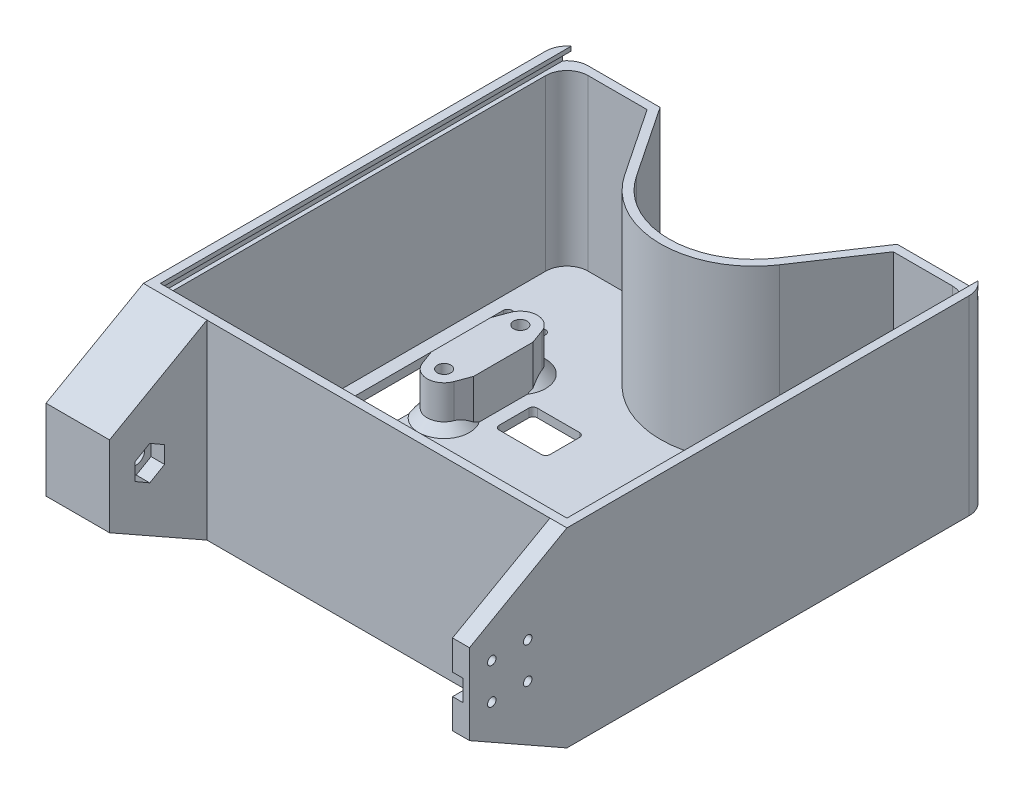
SolidWorks part; units mm, degrees
material "PVC hart"
ref_plane "Ebene vorne" through (0, 0, 0) normal (0, 0, 1) x (1, 0, 0)
ref_plane "Ebene oben" through (0, 0, 0) normal (0, 1, 0) x (1, 0, 0)
ref_plane "Ebene rechts" through (0, 0, 0) normal (1, 0, 0) x (0, 0, -1)
sketch "Grundplatte" plane through (0, 0, 0) normal (0, 1, 0) x (1, 0, 0)
  line L0 (0, 69.0751) -> (0, -94.5087) construction
  line L2 (-50, 50) -> (-50, -50)
  line L3 (-50, -50) -> (50, -50)
  line L4 (50, 50) -> (50, -50)
  line L5 (-50, 50) -> (50, -50) construction
  line L6 (-50, -50) -> (50, 50) construction
  line L7 (-50, 50) -> (-28, 50)
  line L8 (-28, 50) -> (-16.6199, 33)
  line L9 (28, 50) -> (16.6199, 33)
  line L10 (50, 50) -> (28, 50)
  arc A0 (-16.6199, 33) -> (16.6199, 33) centre (0, 44.1257) ccw
  point P0 (0, 0)
  dimension "D4" = 20
  dimension "D1" = 100
  dimension "D2" = 100
  dimension "D3" = 22
  dimension "D5" = 17
extrude "Aufsatz-Linear austragen1" add sketch "Grundplatte" along normal blind 45
shell "Wandung1" thickness 2 removed face at (0, 45, -19.6407)
sketch "Skizze1" plane through (0, 2, 0) normal (0, 1, 0) x (1, 0, 0)
  line L0 (0, 51.8201) -> (0, -55.3816) construction
  line L1 (-28, 50) -> (-50, 50) construction
  line L2 (-45, 31) -> (-35, 31)
  line L3 (-45, 31) -> (-45, -11)
  line L4 (-45, -11) -> (-35, -11)
  line L5 (-35, 31) -> (-35, -11)
  line L6 (-45, 31) -> (-35, -11) construction
  line L7 (-45, -11) -> (-35, 31) construction
  line L8 (50, 50) -> (28, 50) construction
  line L9 (35, 31) -> (45, 31)
  line L10 (35, 31) -> (35, -11)
  line L11 (35, -11) -> (45, -11)
  line L12 (45, 31) -> (45, -11)
  line L13 (35, 31) -> (45, -11) construction
  line L14 (35, -11) -> (45, 31) construction
  point P3 (-40, 10)
  point P10 (40, 10)
  dimension "D1" = 10
  dimension "D2" = 42
  dimension "D3" = 40
  dimension "D4" = 40
  dimension "D5" = 42
  dimension "D6" = 10
  dimension "D7" = 40
  dimension "D8" = 40
extrude "Schnitt-Linear austragen1" cut sketch "Skizze1" against normal up to surface (2 mm away) up to face at (0, 0, -19.6407)
sketch "Skizze2" plane through (0, 2, 0) normal (0, 1, 0) x (1, 0, 0)
  line L20 (-65.457, 10) -> (65.6069, 10) construction
  line L21 (0, 51.8201) -> (0, -54.6693) construction
  line L22 (-35, -11) -> (-35, 31) construction
  line L24 (-35, 16) -> (-35, 4)
  line L26 (-25, 16) -> (-25, 4)
  line L27 (-35, 16) -> (-25, 4) construction
  line L28 (-35, 4) -> (-25, 16) construction
  line L33 (35, 16) -> (35, 17)
  line L34 (33.7533, 20.3831) -> (35, 17)
  line L36 (-35, 16) -> (-35, 17)
  line L37 (-25, 16) -> (-25, 17)
  line L38 (-35, 4) -> (-35, 3)
  line L39 (-25, 4) -> (-25, 3)
  line L40 (-26.2467, 20.3831) -> (-25, 17)
  line L41 (-33.7533, 20.3831) -> (-35, 17)
  line L42 (-26.2467, -0.3831) -> (-25, 3)
  line L43 (-33.7533, -0.3831) -> (-35, 3)
  line L44 (26.2467, 20.3831) -> (25, 17)
  line L45 (25, 16) -> (25, 17)
  line L46 (25, 16) -> (25, 4)
  line L47 (25, 4) -> (25, 3)
  line L48 (26.2467, -0.3831) -> (25, 3)
  line L49 (33.7533, -0.3831) -> (35, 3)
  line L50 (35, 4) -> (35, 3)
  line L51 (35, 16) -> (35, 4)
  circle A4 centre (-30, 19) radius 1.6
  circle A5 centre (-30, 1) radius 1.6
  arc A6 (-26.2467, 20.3831) -> (-33.7533, 20.3831) centre (-30, 19) ccw
  arc A7 (-26.2467, -0.3831) -> (-33.7533, -0.3831) centre (-30, 1) cw
  circle A8 centre (30, 1) radius 1.6
  circle A9 centre (30, 19) radius 1.6
  arc A10 (26.2467, 20.3831) -> (33.7533, 20.3831) centre (30, 19) cw
  arc A11 (26.2467, -0.3831) -> (33.7533, -0.3831) centre (30, 1) ccw
  point P4 (-30, 10)
  point P9 (30, 10)
  dimension "D9" = 3.2
  dimension "D10" = 3.2
  dimension "D13" = 4
  dimension "D14" = 4
  dimension "D2" = 30
  dimension "D3" = 10
  dimension "D5" = 1
  dimension "D6" = 1
  dimension "D7" = 1
  dimension "D8" = 1
  dimension "D11" = 9
  dimension "D12" = 9
extrude "Aufsatz-Linear austragen2" add sketch "Skizze2" along normal blind 10
fillet "Verrundung1" radius 1 8 edges at (35, 1, -31) (45, 1, -31) (35, 1, 11) (45, 1, 11) (-35, 1, 11) (-45, 1, 11) (-45, 1, -31) (-35, 1, -31)
sketch "Skizze6" plane through (0, 12, 0) normal (0, 1, 0) x (1, 0, 0)
  circle A0 centre (-30, 19) radius 1.6
  circle A1 centre (-30, 1) radius 1.6
  circle A2 centre (30, 19) radius 1.6
  circle A3 centre (30, 1) radius 1.6
  dimension "D1" = 3.2
  dimension "D2" = 3.2
  dimension "D3" = 3.2
  dimension "D4" = 3.2
extrude "Schnitt-Linear austragen2" cut sketch "Skizze6" against normal through all
sketch "Skizze7" plane through (0, 0, 0) normal (0, -1, 0) x (1, 0, 0)
  line L0 (0, 58.5427) -> (0, -57.727) construction
  line L1 (-26.7091, -1) -> (-28.3546, 1.85)
  line L2 (-28.3546, 1.85) -> (-31.6454, 1.85)
  line L3 (-31.6454, 1.85) -> (-33.2909, -1)
  line L4 (-33.2909, -1) -> (-31.6454, -3.85)
  line L5 (-31.6454, -3.85) -> (-28.3546, -3.85)
  line L6 (-28.3546, -3.85) -> (-26.7091, -1)
  line L7 (28.3546, -21.85) -> (26.7091, -19)
  line L8 (-26.7091, -19) -> (-28.3546, -16.15)
  line L9 (-28.3546, -16.15) -> (-31.6454, -16.15)
  line L10 (-31.6454, -16.15) -> (-33.2909, -19)
  line L11 (-33.2909, -19) -> (-31.6454, -21.85)
  line L12 (-31.6454, -21.85) -> (-28.3546, -21.85)
  line L13 (-28.3546, -21.85) -> (-26.7091, -19)
  line L14 (31.6454, -21.85) -> (28.3546, -21.85)
  line L15 (33.2909, -19) -> (31.6454, -21.85)
  line L16 (31.6454, -16.15) -> (33.2909, -19)
  line L17 (28.3546, -16.15) -> (31.6454, -16.15)
  line L18 (26.7091, -19) -> (28.3546, -16.15)
  line L19 (28.3546, -3.85) -> (26.7091, -1)
  line L20 (31.6454, -3.85) -> (28.3546, -3.85)
  line L21 (33.2909, -1) -> (31.6454, -3.85)
  line L22 (31.6454, 1.85) -> (33.2909, -1)
  line L23 (28.3546, 1.85) -> (31.6454, 1.85)
  line L24 (26.7091, -1) -> (28.3546, 1.85)
  circle A0 centre (-30, -1) radius 2.85 construction
  circle A1 centre (-30, -19) radius 2.85 construction
  dimension "D1" = 5.7
  dimension "D2" = 5.7
extrude "Schnitt-Linear austragen3" cut sketch "Skizze7" against normal offset from surface (9 mm away) 3 up to face at (30, 12, -2.6)
chamfer "Fase1" distance 2 angle 45 8 edges at (34.3766, 2, -1.3084) (30, 2, 3) (34.3766, 2, -18.6916) (30, 2, -23) (-34.3766, 2, -18.6916) (-30, 2, -23) (-34.3766, 2, -1.3084) (-30, 2, 3)
sketch "Skizze8" plane through (0, 0, 0) normal (0, -1, 0) x (1, 0, 0)
  line L0 (0, 60.6503) -> (0, -60.3099) construction
  line L1 (22, -5) -> (10, -5)
  line L2 (-22, -14) -> (-10, -14)
  line L3 (-22, -14) -> (-22, -5)
  line L4 (-22, -5) -> (-10, -5)
  line L5 (-10, -14) -> (-10, -5)
  line L10 (10, -14) -> (10, -5)
  line L11 (22, -14) -> (10, -14)
  line L12 (22, -14) -> (22, -5)
  circle A0 centre (-30, -1) radius 1.6 construction
  dimension "D2" = 4
  dimension "D1" = 12
  dimension "D3" = 10
  dimension "D4" = 9
extrude "Schnitt-Linear austragen4" cut sketch "Skizze8" against normal up to surface (2 mm away) up to face at (-36.1139, 2, -10)
fillet "Verrundung2" radius 1 8 edges at (-22, 1, -14) (-22, 1, -5) (-10, 1, -5) (-10, 1, -14) (22, 1, -14) (22, 1, -5) (10, 1, -14) (10, 1, -5)
fillet "Verrundung3" radius 5 2 edges at (-50, 22.5, -50) (50, 22.5, -50)
fillet "Verrundung4" radius 5 2 edges at (48, 23.5, -48) (-48, 23.5, -48)
sketch "Skizze9" plane through (0, 0, 0) normal (0, -1, 0) x (1, 0, 0)
  line L0 (0, 54.0796) -> (0, -58.4817) construction
  line L6 (-11, -5) -> (-21, -5) construction
  line L7 (-10.8, 43) -> (10.8, 43)
  line L8 (-12, 41.8) -> (-12, 28.2)
  line L9 (-10.8, 27) -> (10.8, 27)
  line L10 (12, 41.8) -> (12, 28.2)
  line L11 (-12, 43) -> (12, 27) construction
  line L12 (-12, 27) -> (12, 43) construction
  arc A4 (-12, 28.2) -> (-10.8, 27) centre (-10.8, 28.2) ccw
  arc A5 (10.8, 27) -> (12, 28.2) centre (10.8, 28.2) ccw
  arc A6 (10.8, 43) -> (12, 41.8) centre (10.8, 41.8) cw
  arc A7 (-10.8, 43) -> (-12, 41.8) centre (-10.8, 41.8) ccw
  point P3 (0, 35)
  dimension "D4" = 1.2
  dimension "D1" = 16
  dimension "D2" = 24
  dimension "D3" = 40
extrude "Schnitt-Linear austragen5" cut sketch "Skizze9" against normal up to next
sketch "Skizze14" plane through (0, 0, 50) normal (0, 0, 1) x (1, 0, 0)
  line L0 (0, 49.837) -> (0, -24.1023) construction
  line L1 (-50, 45) -> (-50, 0)
  line L2 (-50, 0) -> (-35, 0)
  line L3 (-50, 0) -> (50, 0) construction
  line L4 (-35, 0) -> (-35, 45)
  line L5 (-50, 45) -> (50, 45) construction
  line L6 (-35, 45) -> (-50, 45)
  line L7 (50, 45) -> (46, 45)
  line L8 (46, 45) -> (46, 0)
  line L9 (46, 0) -> (50, 0)
  line L10 (50, 0) -> (50, 45)
  dimension "D1" = 15
  dimension "D2" = 4
extrude "Aufsatz-Linear austragen5" add sketch "Skizze14" along normal blind 23
sketch "Skizze18" plane through (50, 0, 0) normal (1, 0, 0) x (0, 0, -1)
  line L0 (-50, 46.4423) -> (-50, -7.8316) construction
  line L1 (-73, 0) -> (-73, 45) construction
  line L3 (-73, 0) -> (45, 0) construction
  circle A0 centre (-63.5, 22.5) radius 6 construction
  circle A5 centre (-59.2574, 18.2574) radius 1
  circle A9 centre (-67.7426, 18.2574) radius 1
  circle A11 centre (-67.7426, 26.7426) radius 1
  circle A13 centre (-59.2574, 26.7426) radius 1
  point P27 (-63.5, 22.5)
  point P28 (-63.5, 22.5)
  dimension "D2" = 12
  dimension "D5" = 2
  dimension "D6" = 2
  dimension "D7" = 2
  dimension "D8" = 2
  dimension "D1" = 23
  dimension "D3" = 13.5
  dimension "D4" = 22.5
extrude "Schnitt-Linear austragen8" cut sketch "Skizze18" against normal up to surface (4 mm away) up to face at (46, 22.5, 61.5)
sketch "Skizze19" plane through (46, 0, 0) normal (-1, 0, 0) x (0, 0, 1)
  line L0 (50, 40.9842) -> (50, -6.1788) construction
  line L1 (73, 45) -> (73, 0) construction
  line L2 (73, 45) -> (50, 45) construction
  line L3 (63.5, 26.831) -> (63.5, 17.7013) construction
  line L4 (63.5, 25) -> (73, 25)
  line L5 (73, 45) -> (73, 0) construction
  line L6 (63.5, 20) -> (73, 20)
  line L7 (73, 25) -> (73, 20)
  arc A0 (63.5, 25) -> (63.5, 20) centre (63.5, 22.5) ccw
  dimension "D2" = 5
  dimension "D1" = 23
  dimension "D3" = 13.5
  dimension "D4" = 22.5
extrude "Schnitt-Linear austragen9" cut sketch "Skizze19" against normal blind 2.5
sketch "Skizze20" plane through (0, 0, 50) normal (0, 0, 1) x (1, 0, 0)
  line L0 (46, 45) -> (46, 25) construction
  line L1 (41, 27.5) -> (46, 27.5)
  line L2 (41, 27.5) -> (41, 17.5)
  line L3 (41, 17.5) -> (46, 17.5)
  line L4 (46, 27.5) -> (46, 17.5)
  line L5 (41, 27.5) -> (46, 17.5) construction
  line L6 (41, 17.5) -> (46, 27.5) construction
  line L7 (-35, 45) -> (46, 45) construction
  point P0 (43.5, 22.5)
  dimension "D1" = 10
  dimension "D2" = 5
  dimension "D3" = 22.5
extrude "Schnitt-Linear austragen10" cut sketch "Skizze20" against normal up to surface (2 mm away) up to face at (0, 23.5, 48)
sketch "Skizze21" plane through (-50, 0, 0) normal (-1, 0, 0) x (0, 0, 1)
  line L0 (50, 45.8781) -> (50, -12.9091) construction
  line L1 (73, 45) -> (73, 0) construction
  line L2 (-45, 45) -> (73, 45) construction
  circle A0 centre (63.5, 22.5) radius 2
  dimension "D4" = 4
  dimension "D1" = 23
  dimension "D2" = 13.5
  dimension "D3" = 22.5
extrude "Schnitt-Linear austragen11" cut sketch "Skizze21" against normal up to surface (15 mm away) contours A0 up to face at (-35, 22.5, 61.5)
sketch "Skizze23" plane through (-50, 0, 0) normal (-1, 0, 0) x (0, 0, 1)
  circle A0 centre (63.5, 22.5) radius 4
  dimension "D1" = 8
sketch "Skizze26" plane through (-35, 0, 0) normal (1, 0, 0) x (0, 0, -1)
  line L0 (-73, 0) -> (-73, 45) construction
  line L1 (-60, 20.4793) -> (-60, 24.5207)
  line L2 (-60, 24.5207) -> (-63.5, 26.5415)
  line L3 (-63.5, 26.5415) -> (-67, 24.5207)
  line L4 (-67, 24.5207) -> (-67, 20.4793)
  line L5 (-67, 20.4793) -> (-63.5, 18.4585)
  line L6 (-63.5, 18.4585) -> (-60, 20.4793)
  circle A0 centre (-63.5, 22.5) radius 3.5 construction
  dimension "D1" = 7
extrude "Schnitt-Linear austragen14" cut sketch "Skizze26" against normal blind 3.2
sketch "Skizze29" plane through (-50, 0, 0) normal (-1, 0, 0) x (0, 0, 1)
  line L0 (50, 50.1212) -> (50, -3.8482) construction
  line L1 (73, 45) -> (73, 0) construction
  line L2 (73, 45) -> (73, 32)
  line L3 (73, 32) -> (50, 45)
  line L4 (50, 45) -> (73, 45)
  dimension "D1" = 23
  dimension "D2" = 13
extrude "Schnitt-Linear austragen15" cut sketch "Skizze29" against normal up to surface (100 mm away) up to face at (50, 26.7426, 58.2574)
sketch "Skizze31" plane through (0, 0, -50) normal (0, 0, -1) x (-1, 0, 0)
  line L0 (-48, 45) -> (-48, 42)
  line L1 (-45, 45) -> (-50, 45) construction
  line L2 (-48, 42) -> (48, 42)
  line L3 (48, 42) -> (48, 45)
  line L4 (50, 45) -> (45, 45) construction
  line L5 (48, 45) -> (-48, 45)
  line L6 (-50, 0) -> (-50, 45) construction
  line L7 (50, 45) -> (50, 0) construction
  dimension "D1" = 2
  dimension "D2" = 2
  dimension "D3" = 3
extrude "Schnitt-Linear austragen16" cut sketch "Skizze31" against normal blind 30
sketch "Skizze32" plane through (0, 0, -50) normal (0, 0, -1) x (-1, 0, 0)
  line L0 (-48, 45) -> (-50, 45) construction
  line L2 (-49, 44) -> (-49, 42)
  line L3 (-49, 42) -> (49, 42)
  line L4 (49, 42) -> (49, 44)
  line L5 (49, 44) -> (-49, 44)
  line L6 (-50, 0) -> (-50, 45) construction
  line L7 (50, 45) -> (50, 0) construction
  dimension "D1" = 1
  dimension "D2" = 3
  dimension "D3" = 1
  dimension "D4" = 1
extrude "Schnitt-Linear austragen17" cut sketch "Skizze32" against normal blind 99
sketch "Skizze33" plane through (50, 0, 0) normal (1, 0, 0) x (0, 0, -1)
  line L0 (-50, 51.8362) -> (-50, -5.0941) construction
  line L1 (-73, 0) -> (-73, 32) construction
  line L2 (-50, 0) -> (-73, 13)
  line L3 (-73, 13) -> (-73, 0)
  line L4 (-73, 0) -> (-50, 0)
  dimension "D1" = 23
  dimension "D2" = 13
extrude "Schnitt-Linear austragen18" cut sketch "Skizze33" against normal up to surface (100 mm away) up to face at (-50, 22.5, 65.5)
sketch "Skizze34" plane through (0, 2, 0) normal (0, 1, 0) x (1, 0, 0)
  line L21 (10.8, -27) -> (-10.8, -27)
  line L22 (-12, -28.2) -> (-12, -41.8)
  line L23 (-10.8, -43) -> (10.8, -43)
  line L24 (12, -41.8) -> (12, -28.2)
  line L25 (14, -41.8) -> (14, -28.2)
  line L26 (-10.8, -45) -> (10.8, -45)
  line L27 (-14, -28.2) -> (-14, -41.8)
  line L28 (10.8, -25) -> (-10.8, -25)
  line L29 (14, -41.8) -> (14, -28.2)
  line L30 (-10.8, -45) -> (10.8, -45)
  line L31 (-14, -28.2) -> (-14, -41.8)
  line L32 (10.8, -25) -> (-10.8, -25)
  arc A15 (-10.8, -27) -> (-12, -28.2) centre (-10.8, -28.2) ccw
  arc A16 (-12, -41.8) -> (-10.8, -43) centre (-10.8, -41.8) ccw
  arc A17 (10.8, -43) -> (12, -41.8) centre (10.8, -41.8) ccw
  arc A18 (12, -28.2) -> (10.8, -27) centre (10.8, -28.2) ccw
  arc A19 (14, -28.2) -> (10.8, -25) centre (10.8, -28.2) ccw
  arc A20 (10.8, -45) -> (14, -41.8) centre (10.8, -41.8) ccw
  arc A21 (-14, -41.8) -> (-10.8, -45) centre (-10.8, -41.8) ccw
  arc A22 (-10.8, -25) -> (-14, -28.2) centre (-10.8, -28.2) ccw
  arc A23 (14, -28.2) -> (10.8, -25) centre (10.8, -28.2) ccw
  arc A24 (10.8, -45) -> (14, -41.8) centre (10.8, -41.8) ccw
  arc A25 (-14, -41.8) -> (-10.8, -45) centre (-10.8, -41.8) ccw
  arc A26 (-10.8, -25) -> (-14, -28.2) centre (-10.8, -28.2) ccw
  dimension "D1" = 2
  dimension "D2" = 2
extrude "Aufsatz-Linear austragen6" add sketch "Skizze34" along normal blind 12
sketch "Skizze35" plane through (0, 14, 0) normal (0, 1, 0) x (1, 0, 0)
  line L24 (14, -41.8) -> (14, -28.2)
  line L25 (-10.8, -45) -> (10.8, -45)
  line L26 (-14, -28.2) -> (-14, -41.8)
  line L27 (10.8, -25) -> (-10.8, -25)
  line L28 (14, -41.8) -> (14, -28.2)
  line L29 (-10.8, -45) -> (10.8, -45)
  line L30 (-14, -28.2) -> (-14, -41.8)
  line L31 (10.8, -25) -> (-10.8, -25)
  arc A20 (14, -28.2) -> (10.8, -25) centre (10.8, -28.2) ccw
  arc A21 (10.8, -45) -> (14, -41.8) centre (10.8, -41.8) ccw
  arc A22 (-14, -41.8) -> (-10.8, -45) centre (-10.8, -41.8) ccw
  arc A23 (-10.8, -25) -> (-14, -28.2) centre (-10.8, -28.2) ccw
  arc A24 (14, -28.2) -> (10.8, -25) centre (10.8, -28.2) ccw
  arc A25 (10.8, -45) -> (14, -41.8) centre (10.8, -41.8) ccw
  arc A26 (-14, -41.8) -> (-10.8, -45) centre (-10.8, -41.8) ccw
  arc A27 (-10.8, -25) -> (-14, -28.2) centre (-10.8, -28.2) ccw
  dimension "D1" = 2
extrude "Aufsatz-Linear austragen7" add sketch "Skizze35" along normal blind 2
sketch "Skizze36" plane through (0, 16, 0) normal (0, 1, 0) x (1, 0, 0)
  line L0 (0, -19.7815) -> (0, -45.8796) construction
  line L1 (-10.8, -45) -> (10.8, -45) construction
  circle A0 centre (8, -35) radius 1.6
  circle A1 centre (-8, -35) radius 1.6
  dimension "D1" = 3.2
  dimension "D2" = 16
  dimension "D3" = 10
extrude "Schnitt-Linear austragen19" cut sketch "Skizze36" against normal up to surface (2 mm away) up to face at (0, 14, 35)
chamfer "Fase2" distance 2 angle 45 8 edges at (13.0627, 2, 44.0627) (0, 2, 45) (-13.0627, 2, 44.0627) (-14, 2, 35) (-13.0627, 2, 25.9373) (0, 2, 25) (13.0627, 2, 25.9373) (14, 2, 35)
extrude "Schnitt-Linear austragen20" cut sketch "Skizze23" against normal blind 2 draft 45
